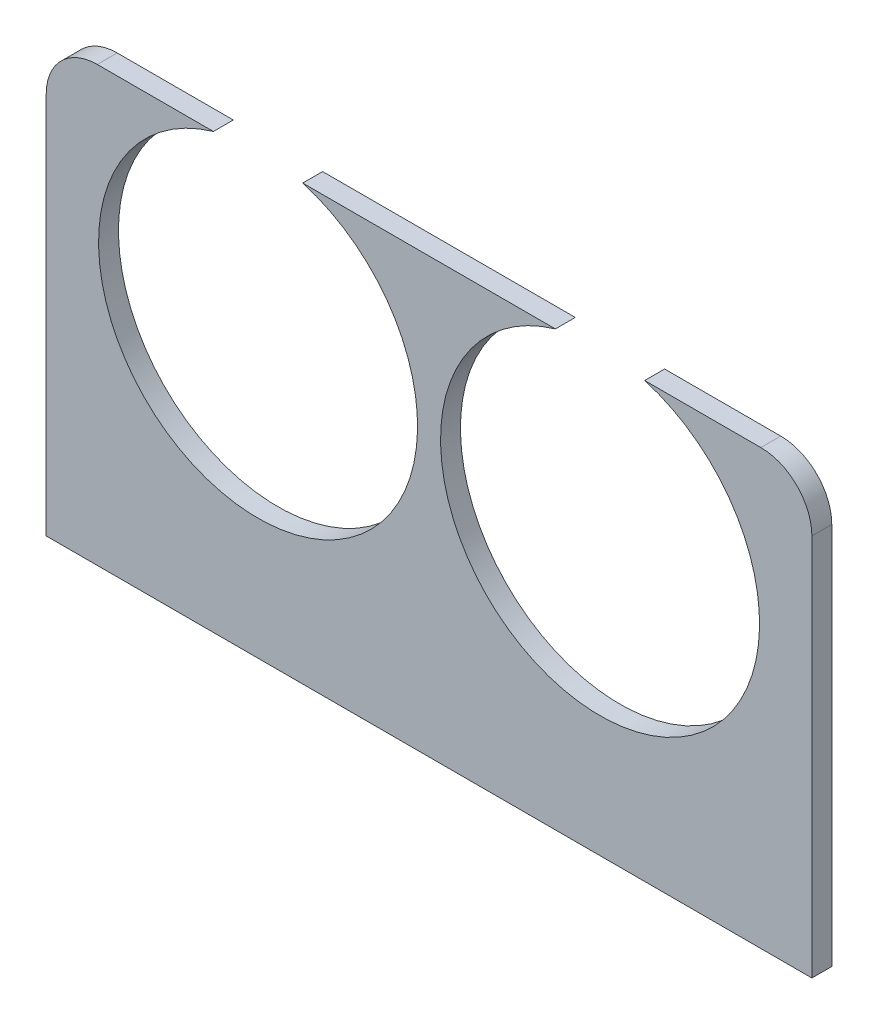
SolidWorks part; units mm, degrees
ref_plane "Front Plane" through (0, 0, 0) normal (0, 0, 1) x (1, 0, 0)
ref_plane "Top Plane" through (0, 0, 0) normal (0, 1, 0) x (1, 0, 0)
ref_plane "Right Plane" through (0, 0, 0) normal (1, 0, 0) x (0, 0, -1)
sketch "Sketch1" plane through (0, 0, 0) normal (0, 0, 1) x (1, 0, 0)
  line L0 (-6.7, 2.5) -> (6.7, 2.5) construction
  line L1 (-15, -8.5) -> (15, -8.5)
  line L2 (-15, -8.5) -> (-15, 8.5)
  line L3 (-15, 8.5) -> (15, 8.5)
  line L4 (15, -8.5) -> (15, 8.5)
  line L5 (-15, -8.5) -> (15, 8.5) construction
  line L6 (-15, 8.5) -> (15, -8.5) construction
  line L7 (-15, 2.5) -> (15, 2.5) construction
  circle A0 centre (-6.7, 2.5) radius 6.25
  circle A1 centre (6.7, 2.5) radius 6.25
  point P4 (0, 0)
  point P6 (0, 2.5)
  dimension "D1" = 12.5
  dimension "D2" = 13.4
  dimension "D3" = 6
  dimension "D4" = 30
  dimension "D5" = 17
extrude "Boss-Extrude1" add sketch "Sketch1" along normal blind 0.78 contours L3 A1 A0 L2 L1 L4 region at (0, -2.2711, 0)
fillet "Fillet1" radius 2 2 edges at (15, 8.5, 0.39) (-15, 8.5, 0.39)
sketch "Sketch2" plane through (0, 0, 0.78) normal (0, 0, 1) x (1, 0, 0)
  line L1 (-9.09, -5.265) -> (9.09, -5.265) construction
  line L2 (-9.09, -5.265) -> (-9.09, -6.935) construction
  line L3 (-9.09, -6.935) -> (9.09, -6.935) construction
  line L4 (9.09, -5.265) -> (9.09, -6.935) construction
  line L5 (-9.09, -5.265) -> (9.09, -6.935) construction
  line L6 (-9.09, -6.935) -> (9.09, -5.265) construction
  point P4 (0, -6.1)
  point P7 (0, 0)
  point P8 (0, 0)
